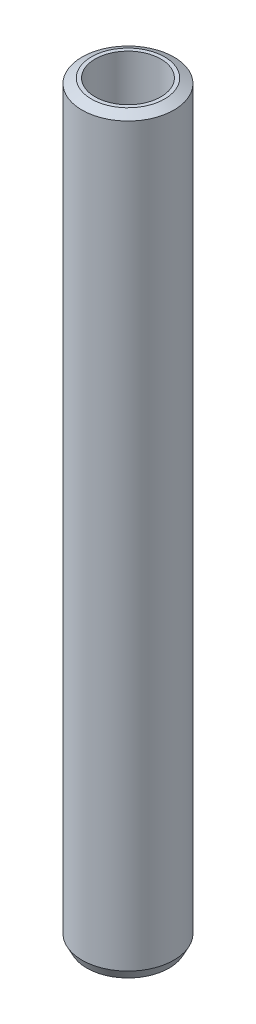
SolidWorks part; units mm, degrees
ref_plane "Front Plane" through (0, 0, 0) normal (0, 0, 1) x (1, 0, 0)
ref_plane "Top Plane" through (0, 0, 0) normal (0, 1, 0) x (1, 0, 0)
ref_plane "Right Plane" through (0, 0, 0) normal (1, 0, 0) x (0, 0, -1)
sketch "Sketch1" plane through (0, 0, 0) normal (0, 1, 0) x (1, 0, 0)
  circle A0 centre (0, 0) radius 32.5
  dimension "SHAFT_OD" = 65
extrude "Boss-Extrude1" add sketch "Sketch1" along normal blind 530.4493
sketch "Sketch2" plane through (0, 0, 0) normal (0, 1, 0) x (1, 0, 0)
  circle A0 centre (0, 0) radius 23.2295
  dimension "BORE_D" = 46.4591
extrude "Cut-Extrude1" cut sketch "Sketch2" along normal through all
chamfer "Chamfer1" distance 3.4307 angle 62.67 2 edges at (0, 530.4493, 32.5) (0, 0, 32.5) first distance on face at (0, 530.4493, 32.5) first distance on face at (0, 0, 23.2295)
